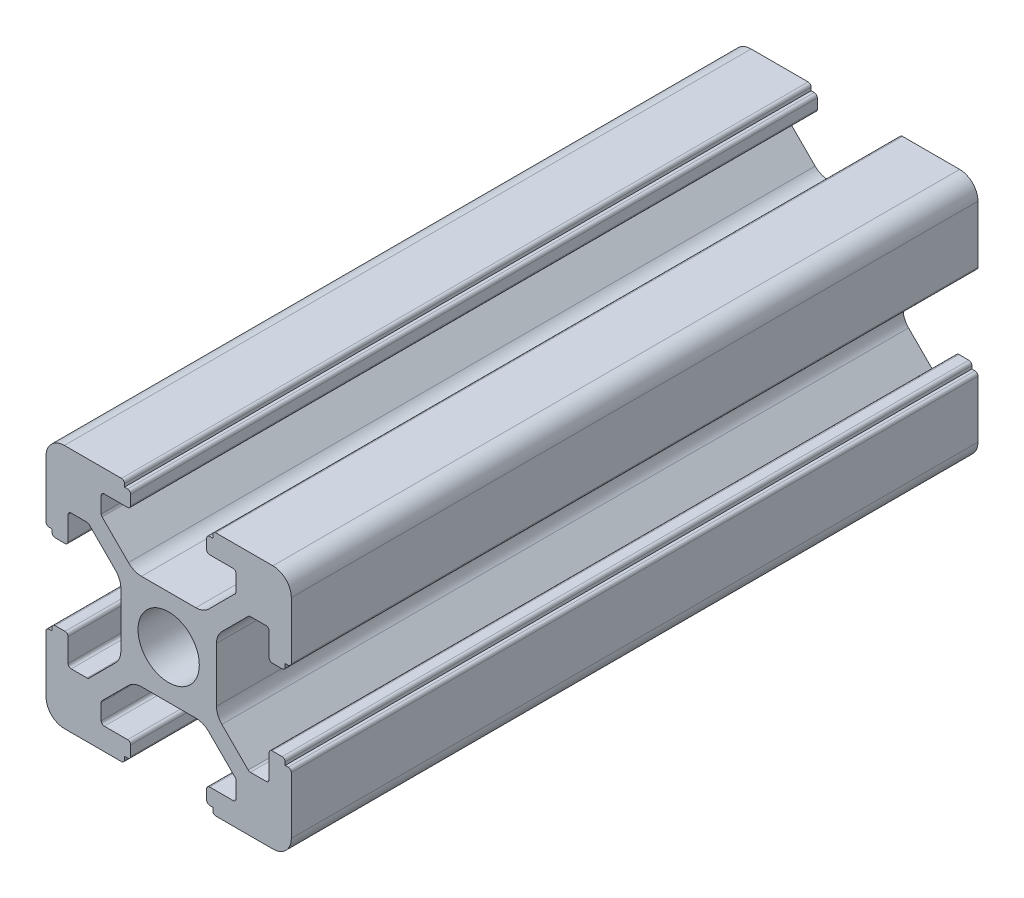
SolidWorks part; units mm, degrees
ref_plane "前视基准面" through (0, 0, 0) normal (0, 0, 1) x (1, 0, 0)
ref_plane "上视基准面" through (0, 0, 0) normal (0, 1, 0) x (1, 0, 0)
ref_plane "右视基准面" through (0, 0, 0) normal (1, 0, 0) x (0, 0, -1)
sketch "草图1" plane through (0, 0, 0) normal (0, 0, 1) x (1, 0, 0)
  line L0 (0, 0) -> (0, 5.5) construction
  line L1 (-8.5023, -10.0023) -> (-3.85, -10.0023)
  line L2 (-10.0023, -8.5023) -> (-10.0023, -3.85)
  line L3 (-8.5023, 10.0023) -> (-3.85, 10.0023)
  line L4 (10.0023, -8.5023) -> (10.0023, -3.85)
  line L5 (-10.0023, -10.0023) -> (10.0023, 10.0023) construction
  line L6 (-10.0023, 10.0023) -> (10.0023, -10.0023) construction
  line L7 (-2.218, -3.9) -> (2.218, -3.9)
  line L8 (-3.9, -2.218) -> (-3.9, 2.218)
  line L9 (-2.218, 3.9) -> (2.218, 3.9)
  line L10 (3.9, -2.218) -> (3.9, 2.218)
  line L11 (-3.9, -3.9) -> (3.9, 3.9) construction
  line L12 (-3.9, 3.9) -> (3.9, -3.9) construction
  line L13 (-5.25, -8.2) -> (-3.35, -8.2)
  line L14 (-8.2, -5.25) -> (-8.2, -3.35)
  line L15 (-5.25, 8.2) -> (-3.35, 8.2)
  line L16 (8.2, -5.25) -> (8.2, -3.35)
  line L17 (-8.2, -8.2) -> (8.2, 8.2) construction
  line L18 (-8.2, 8.2) -> (8.2, -8.2) construction
  line L19 (-7.95, 5.5) -> (-6.6642, 5.5)
  line L20 (0, 0) -> (5.5, 0) construction
  line L23 (-5.5, 7.95) -> (-5.5, 6.6642)
  line L26 (0, 0) -> (-0.5303, 0.5303)
  line L27 (3.2787, 4.3393) -> (5.4268, 6.4874)
  line L28 (0, 0) -> (0.5303, -0.5303)
  line L29 (5.5, 6.6642) -> (5.5, 7.95)
  line L30 (4.3393, 3.2787) -> (6.4874, 5.4268)
  line L31 (6.6642, 5.5) -> (7.95, 5.5)
  line L32 (4.3393, -3.2787) -> (6.4874, -5.4268)
  line L33 (3.2787, -4.3393) -> (5.4268, -6.4874)
  line L34 (-3.2787, -4.3393) -> (-5.4268, -6.4874)
  line L35 (-4.3393, -3.2787) -> (-6.4874, -5.4268)
  line L36 (-4.3393, 3.2787) -> (-6.4874, 5.4268)
  line L37 (-3.2787, 4.3393) -> (-5.4268, 6.4874)
  line L38 (3.1, -8.45) -> (3.1, -9.2523)
  line L39 (8.45, 3.1) -> (9.2523, 3.1)
  line L40 (-5.5, -6.6642) -> (-5.5, -7.95)
  line L41 (-6.6642, -5.5) -> (-7.95, -5.5)
  line L42 (5.5, -6.6642) -> (5.5, -7.95)
  line L43 (6.6642, -5.5) -> (7.95, -5.5)
  line L44 (9.2523, -3.1) -> (8.45, -3.1)
  line L46 (10.0023, 3.85) -> (10.0023, 8.5023)
  line L47 (8.2, 3.35) -> (8.2, 5.25)
  line L48 (-3.1, -9.2523) -> (-3.1, -8.45)
  line L49 (-8.45, -3.1) -> (-9.2523, -3.1)
  line L50 (-9.2523, 3.1) -> (-8.45, 3.1)
  line L51 (-3.1, 8.45) -> (-3.1, 9.2523)
  line L52 (3.1, 9.2523) -> (3.1, 8.45)
  line L53 (3.85, 10.0023) -> (8.5023, 10.0023)
  line L54 (3.35, 8.2) -> (5.25, 8.2)
  line L55 (-10.0023, 3.85) -> (-10.0023, 8.5023)
  line L56 (-8.2, 3.35) -> (-8.2, 5.25)
  line L57 (3.35, -8.2) -> (5.25, -8.2)
  line L58 (3.85, -10.0023) -> (8.5023, -10.0023)
  line L59 (9.7523, -3.6) -> (9.5023, -3.6)
  line L61 (9.7523, 3.6) -> (9.5023, 3.6)
  line L62 (9.5023, -3.6) -> (9.5023, -3.35)
  line L63 (3.6, -9.7523) -> (3.6, -9.5023)
  line L64 (3.35, -9.5023) -> (3.6, -9.5023)
  line L65 (9.5023, 3.35) -> (9.5023, 3.6)
  line L66 (-3.6, -9.5023) -> (-3.35, -9.5023)
  line L67 (-3.6, -9.7523) -> (-3.6, -9.5023)
  line L68 (-9.7523, -3.6) -> (-9.5023, -3.6)
  line L69 (-9.5023, -3.35) -> (-9.5023, -3.6)
  line L70 (-9.5023, 3.6) -> (-9.5023, 3.35)
  line L71 (-9.7523, 3.6) -> (-9.5023, 3.6)
  line L72 (-3.6, 9.7523) -> (-3.6, 9.5023)
  line L73 (-3.35, 9.5023) -> (-3.6, 9.5023)
  line L74 (3.6, 9.5023) -> (3.35, 9.5023)
  line L75 (3.6, 9.7523) -> (3.6, 9.5023)
  circle A0 centre (0, 0) radius 2.5
  arc A1 (10.0023, 8.5023) -> (8.5023, 10.0023) centre (8.5023, 8.5023) ccw
  arc A2 (8.5023, -10.0023) -> (10.0023, -8.5023) centre (8.5023, -8.5023) ccw
  arc A3 (-10.0023, -8.5023) -> (-8.5023, -10.0023) centre (-8.5023, -8.5023) ccw
  arc A4 (-10.0023, 8.5023) -> (-8.5023, 10.0023) centre (-8.5023, 8.5023) cw
  arc A5 (-9.5023, -3.35) -> (-9.2523, -3.1) centre (-9.2523, -3.35) cw
  arc A6 (-9.7523, -3.6) -> (-10.0023, -3.85) centre (-9.7523, -3.85) ccw
  arc A7 (-8.45, -3.1) -> (-8.2, -3.35) centre (-8.45, -3.35) cw
  arc A8 (-7.95, -5.5) -> (-8.2, -5.25) centre (-7.95, -5.25) cw
  arc A9 (-6.4874, -5.4268) -> (-6.6642, -5.5) centre (-6.6642, -5.25) cw
  arc A10 (-5.4268, -6.4874) -> (-5.5, -6.6642) centre (-5.25, -6.6642) ccw
  arc A11 (-5.5, -7.95) -> (-5.25, -8.2) centre (-5.25, -7.95) ccw
  arc A12 (-3.6, -9.7523) -> (-3.85, -10.0023) centre (-3.85, -9.7523) cw
  arc A13 (-3.35, -9.5023) -> (-3.1, -9.2523) centre (-3.35, -9.2523) ccw
  arc A14 (-3.1, -8.45) -> (-3.35, -8.2) centre (-3.35, -8.45) ccw
  arc A15 (3.1, -8.45) -> (3.35, -8.2) centre (3.35, -8.45) cw
  arc A16 (5.5, -7.95) -> (5.25, -8.2) centre (5.25, -7.95) cw
  arc A17 (5.4268, -6.4874) -> (5.5, -6.6642) centre (5.25, -6.6642) cw
  arc A18 (6.4874, -5.4268) -> (6.6642, -5.5) centre (6.6642, -5.25) ccw
  arc A19 (7.95, -5.5) -> (8.2, -5.25) centre (7.95, -5.25) ccw
  arc A20 (8.45, -3.1) -> (8.2, -3.35) centre (8.45, -3.35) ccw
  arc A21 (9.5023, -3.35) -> (9.2523, -3.1) centre (9.2523, -3.35) ccw
  arc A22 (9.7523, -3.6) -> (10.0023, -3.85) centre (9.7523, -3.85) cw
  arc A23 (3.35, -9.5023) -> (3.1, -9.2523) centre (3.35, -9.2523) cw
  arc A24 (3.6, -9.7523) -> (3.85, -10.0023) centre (3.85, -9.7523) ccw
  arc A25 (7.95, 5.5) -> (8.2, 5.25) centre (7.95, 5.25) cw
  arc A26 (8.2, 3.35) -> (8.45, 3.1) centre (8.45, 3.35) ccw
  arc A27 (9.5023, 3.35) -> (9.2523, 3.1) centre (9.2523, 3.35) cw
  arc A28 (9.7523, 3.6) -> (10.0023, 3.85) centre (9.7523, 3.85) ccw
  arc A29 (6.6642, 5.5) -> (6.4874, 5.4268) centre (6.6642, 5.25) ccw
  arc A30 (5.4268, 6.4874) -> (5.5, 6.6642) centre (5.25, 6.6642) ccw
  arc A31 (5.5, 7.95) -> (5.25, 8.2) centre (5.25, 7.95) ccw
  arc A32 (3.1, 8.45) -> (3.35, 8.2) centre (3.35, 8.45) ccw
  arc A33 (3.6, 9.7523) -> (3.85, 10.0023) centre (3.85, 9.7523) cw
  arc A34 (3.35, 9.5023) -> (3.1, 9.2523) centre (3.35, 9.2523) ccw
  arc A35 (-9.7523, 3.6) -> (-10.0023, 3.85) centre (-9.7523, 3.85) cw
  arc A36 (-9.5023, 3.35) -> (-9.2523, 3.1) centre (-9.2523, 3.35) ccw
  arc A37 (-8.45, 3.1) -> (-8.2, 3.35) centre (-8.45, 3.35) ccw
  arc A38 (-8.2, 5.25) -> (-7.95, 5.5) centre (-7.95, 5.25) cw
  arc A39 (-6.4874, 5.4268) -> (-6.6642, 5.5) centre (-6.6642, 5.25) ccw
  arc A40 (-5.4268, 6.4874) -> (-5.5, 6.6642) centre (-5.25, 6.6642) cw
  arc A41 (-5.5, 7.95) -> (-5.25, 8.2) centre (-5.25, 7.95) cw
  arc A42 (-3.1, 8.45) -> (-3.35, 8.2) centre (-3.35, 8.45) cw
  arc A43 (-3.1, 9.2523) -> (-3.35, 9.5023) centre (-3.35, 9.2523) ccw
  arc A44 (-3.6, 9.7523) -> (-3.85, 10.0023) centre (-3.85, 9.7523) ccw
  arc A45 (-4.3393, 3.2787) -> (-3.9, 2.218) centre (-5.4, 2.218) cw
  arc A46 (-3.2787, 4.3393) -> (-2.218, 3.9) centre (-2.218, 5.4) ccw
  arc A47 (3.2787, 4.3393) -> (2.218, 3.9) centre (2.218, 5.4) cw
  arc A48 (4.3393, 3.2787) -> (3.9, 2.218) centre (5.4, 2.218) ccw
  arc A49 (4.3393, -3.2787) -> (3.9, -2.218) centre (5.4, -2.218) cw
  arc A50 (3.2787, -4.3393) -> (2.218, -3.9) centre (2.218, -5.4) ccw
  arc A51 (-4.3393, -3.2787) -> (-3.9, -2.218) centre (-5.4, -2.218) ccw
  arc A52 (-2.218, -3.9) -> (-3.2787, -4.3393) centre (-2.218, -5.4) ccw
  point P0 (0, 0)
  point P7 (10.0023, 0)
  point P62 (0, 0)
  point P76 (0, 0)
  point P92 (-8.2, -5.5)
  point P99 (0, 0)
  point P106 (-5.5, -8.2)
  point P117 (5.5, -8.2)
  point P124 (8.2, -5.5)
  point P137 (8.2, 5.5)
  point P140 (8.2, 3.1)
  point P147 (6.5607, 5.5)
  point P152 (5.5, 8.2)
  point P167 (-8.2, 5.5)
  point P174 (-5.5, 8.2)
  dimension "D1" = 1.5
  dimension "D5" = 0.25
  dimension "D6" = 1.5
  dimension "D2" = 4
  dimension "D3" = 4
  dimension "D4" = 4
extrude "凸台-拉伸1" add sketch "草图1" along normal blind 56 contours A52 L7 A50 L33 A17 L42 A16 L57 A15 L38 A23 L64 L63 A24 L58 A2 L4 A22 L59 L62 A21 L44 A20 L16 A19 L43 A18 L32 A49 L10 A48 L30 A29 L31 A25 L47 A26 L39 A27 L65 L61 A28 L46 A1 L53 A33 L75 L74 A34 L52 A32 region at (-9.3629, -9.3629, 0)
